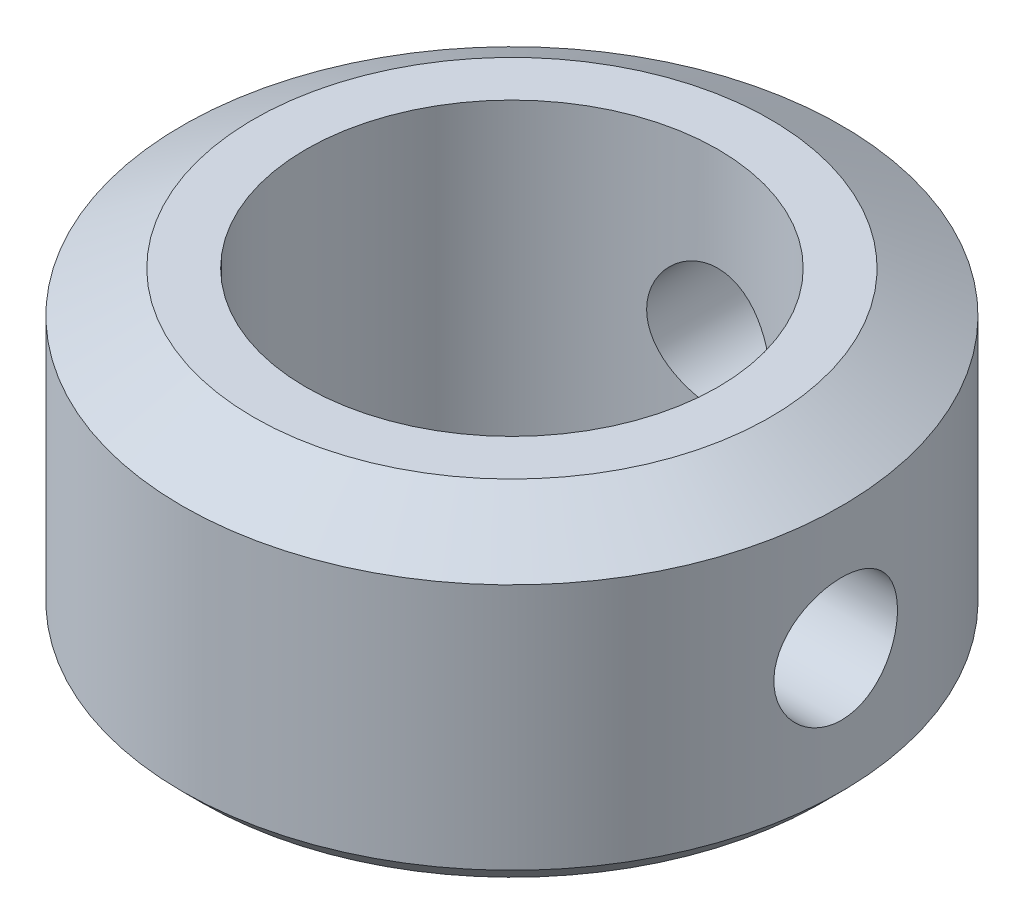
SolidWorks part; units mm, degrees
note: '?' marks a value the reader was unsure of.
material "1060 Alloy"
ref_plane "Front Plane" through (0, 0, 0) normal (0, 0, 1) x (1, 0, 0)
ref_plane "Top Plane" through (0, 0, 0) normal (0, 1, 0) x (1, 0, 0)
ref_plane "Right Plane" through (0, 0, 0) normal (1, 0, 0) x (0, 0, -1)
sketch "Sketch1" plane through (0, 0, 0) normal (0, 1, 0) x (1, 0, 0)
  circle A0 centre (0, 0) radius 5
  circle A1 centre (0, 0) radius 8
  dimension "D1" = 10
  dimension "D2" = 16
extrude "Boss-Extrude1" add sketch "Sketch1" along normal blind 7.5
chamfer "Chamfer1" distance 1 angle 60 1 edges at (0, 7.5, 8)
chamfer "Chamfer2" distance 0.5 angle 45 1 edges at (0, 0, 8)
chamfer "Chamfer3" distance 0.2 angle 45 1 edges at (0, 0, 5)
ref_plane "Plane1" through (8, 0, 0) normal (1, 0, 0) x (0, 0, -1)
sketch "Sketch2" plane through (8, 0, 0) normal (1, 0, 0) x (0, 0, -1)
  line L0 (-8, 0.5) -> (8, 0.5) construction
  line L3 (0, 6.5) -> (0, 0.5) construction
  line L4 (-8, 6.5) -> (8, 6.5) construction
  circle A0 centre (0, 3.5) radius 1.5
  dimension "D1" = 3
  dimension "D2" = 3.5
extrude "Cut-Extrude1" cut sketch "Sketch2" against normal up to next
ref_axis "Axis1" through (0, 7.5, 0) along (0, -1, 0)?
pattern_circular "CirPattern1" count 2 every 90 about axis through (0, 7.5, 0) along (0, -1, 0) of "Cut-Extrude1"
